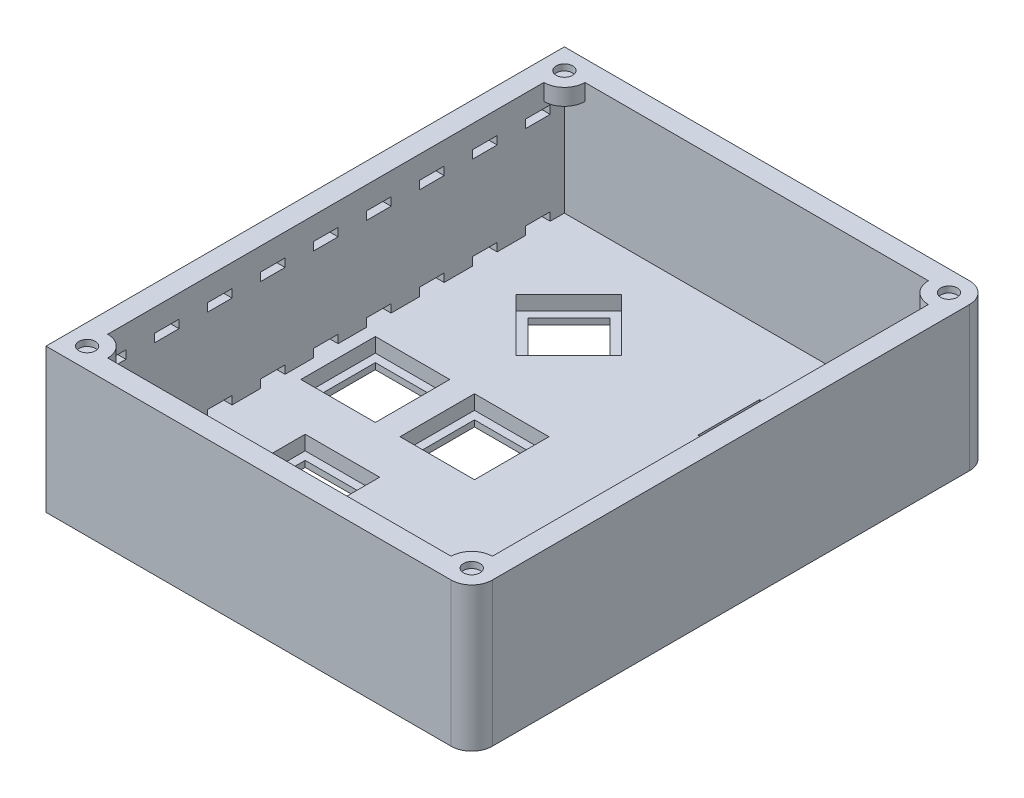
SolidWorks part; units mm, degrees
ref_plane "Front Plane" through (0, 0, 0) normal (0, 0, 1) x (1, 0, 0)
ref_plane "Top Plane" through (0, 0, 0) normal (0, 1, 0) x (1, 0, 0)
ref_plane "Right Plane" through (0, 0, 0) normal (1, 0, 0) x (0, 0, -1)
sketch "Sketch1" plane through (0, 0, 0) normal (0, 1, 0) x (1, 0, 0)
  line L0 (93.4844, 127.7999) -> (93.4844, -14.5462) construction
  line L1 (0, 0) -> (186.9688, 0)
  line L2 (0, 0) -> (0, 116)
  line L3 (0, 116) -> (186.9688, 116)
  line L4 (186.9688, 0) -> (186.9688, 116)
  line L25 (69.3844, 113.4279) -> (69.3844, 11.6856) construction
  line L26 (50.2844, 65.05) -> (64.3844, 65.05)
  line L31 (50.2844, 65.05) -> (50.2844, 50.95)
  line L32 (50.2844, 50.95) -> (64.3844, 50.95)
  line L33 (27.175, 93) -> (0, 93) construction
  line L34 (23, 88.825) -> (23, 116) construction
  line L35 (64.3844, 65.05) -> (64.3844, 50.95)
  line L40 (47.7844, 67.55) -> (47.7844, 48.45)
  line L41 (47.7844, 48.45) -> (66.8844, 48.45)
  line L42 (66.8844, 67.55) -> (66.8844, 48.45)
  line L43 (47.7844, 67.55) -> (66.8844, 67.55)
  line L44 (90.9844, 67.55) -> (90.9844, 48.45)
  line L45 (90.9844, 48.45) -> (71.8844, 48.45)
  line L46 (71.8844, 67.55) -> (71.8844, 48.45)
  line L47 (90.9844, 67.55) -> (71.8844, 67.55)
  line L48 (88.4844, 50.95) -> (74.3844, 50.95)
  line L49 (74.3844, 65.05) -> (74.3844, 50.95)
  line L50 (88.4844, 65.05) -> (74.3844, 65.05)
  line L51 (88.4844, 65.05) -> (88.4844, 50.95)
  line L52 (13.3874, 28.9) -> (54.844, 28.9) construction
  line L53 (62.3344, 35.95) -> (76.4344, 35.95)
  line L54 (62.3344, 35.95) -> (62.3344, 21.85)
  line L63 (62.3344, 21.85) -> (76.4344, 21.85)
  line L64 (-34.0049, 58) -> (152.0549, 58) construction
  line L65 (76.4344, 35.95) -> (76.4344, 21.85)
  line L66 (50.3844, 38.45) -> (88.3844, 38.45)
  line L67 (50.3844, 38.45) -> (50.3844, 19.35)
  line L68 (50.3844, 19.35) -> (88.3844, 19.35)
  line L69 (88.3844, 38.45) -> (88.3844, 19.35)
  line L70 (136.5844, 19.35) -> (98.5844, 19.35)
  line L71 (98.5844, 38.45) -> (98.5844, 19.35)
  line L72 (136.5844, 38.45) -> (98.5844, 38.45)
  line L73 (136.5844, 38.45) -> (136.5844, 19.35)
  line L74 (124.6344, 21.85) -> (110.5344, 21.85)
  line L75 (110.5344, 35.95) -> (110.5344, 21.85)
  line L76 (124.6344, 35.95) -> (110.5344, 35.95)
  line L77 (124.6344, 35.95) -> (124.6344, 21.85)
  line L78 (98.4844, 65.05) -> (98.4844, 50.95)
  line L79 (98.4844, 65.05) -> (112.5844, 65.05)
  line L80 (112.5844, 65.05) -> (112.5844, 50.95)
  line L81 (98.4844, 50.95) -> (112.5844, 50.95)
  line L82 (95.9844, 48.45) -> (115.0844, 48.45)
  line L83 (95.9844, 67.55) -> (95.9844, 48.45)
  line L84 (95.9844, 67.55) -> (115.0844, 67.55)
  line L85 (115.0844, 67.55) -> (115.0844, 48.45)
  line L86 (139.1844, 48.45) -> (120.0844, 48.45)
  line L87 (139.1844, 67.55) -> (139.1844, 48.45)
  line L88 (139.1844, 67.55) -> (120.0844, 67.55)
  line L89 (120.0844, 67.55) -> (120.0844, 48.45)
  line L90 (136.6844, 50.95) -> (122.5844, 50.95)
  line L91 (122.5844, 65.05) -> (122.5844, 50.95)
  line L92 (136.6844, 65.05) -> (122.5844, 65.05)
  line L93 (136.6844, 65.05) -> (136.6844, 50.95)
  line L94 (66.8844, 58.1269) -> (71.8844, 58.1269) construction
  line L95 (90.9844, 58.1269) -> (95.9844, 58.1269) construction
  line L96 (38, 113.0349) -> (38, 79.1538) construction
  line L97 (69.3844, 102.9702) -> (59.4142, 93)
  line L102 (59.4142, 93) -> (69.3844, 83.0298)
  line L103 (69.3844, 83.0298) -> (79.3546, 93)
  line L104 (79.3546, 93) -> (69.3844, 102.9702)
  line L109 (80.7688, 93) -> (69.3844, 104.3844)
  line L110 (69.3844, 104.3844) -> (58, 93)
  line L111 (58, 93) -> (69.3844, 81.6156)
  line L112 (69.3844, 81.6156) -> (80.7688, 93)
  line L113 (117.5844, 81.6156) -> (106.2, 93)
  line L114 (128.9688, 93) -> (117.5844, 81.6156)
  line L115 (117.5844, 104.3844) -> (128.9688, 93)
  line L116 (106.2, 93) -> (117.5844, 104.3844)
  line L117 (117.5844, 83.0298) -> (107.6142, 93)
  line L118 (127.5546, 93) -> (117.5844, 83.0298)
  line L119 (117.5844, 102.9702) -> (127.5546, 93)
  line L120 (107.6142, 93) -> (117.5844, 102.9702)
  line L121 (-5, 0) -> (-5, 116)
  line L122 (0, 121) -> (186.9688, 121)
  line L123 (191.9688, 0) -> (191.9688, 116)
  line L124 (0, -5) -> (186.9688, -5)
  line L125 (191.9688, -5) -> (191.9688, 121) construction
  line L126 (-5, -5) -> (191.9688, -5) construction
  line L127 (-5, 121) -> (191.9688, 121) construction
  line L128 (-5, -5) -> (-5, 121) construction
  line L129 (169.3688, 91.75) -> (158.5688, 91.75)
  line L130 (17.6, 94.25) -> (28.4, 94.25)
  line L131 (17.6, 94.25) -> (17.6, 91.75)
  line L132 (17.6, 91.75) -> (28.4, 91.75)
  line L133 (28.4, 94.25) -> (28.4, 91.75)
  line L134 (158.5688, 94.25) -> (158.5688, 91.75)
  line L135 (169.3688, 94.25) -> (158.5688, 94.25)
  line L136 (169.3688, 94.25) -> (169.3688, 91.75)
  line L137 (23, 88.825) -> (23, 58) construction
  line L138 (27.175, 93) -> (58, 93) construction
  circle A0 centre (23, 93) radius 4.175
  circle A2 centre (23, 93) radius 15
  circle A3 centre (163.9688, 93) radius 15
  circle A4 centre (163.9688, 93) radius 4.175
  arc A6 (0, 121) -> (-5, 116) centre (0, 116) ccw
  arc A7 (-5, 0) -> (0, -5) centre (0, 0) ccw
  arc A8 (186.9688, -5) -> (191.9688, 0) centre (186.9688, 0) ccw
  arc A9 (191.9688, 116) -> (186.9688, 121) centre (186.9688, 116) ccw
  point P31 (69.3844, 35.95)
  point P33 (93.4844, 116)
  point P37 (69.3844, 38.45)
  point P40 (88.3844, 28.9)
  point P41 (76.4344, 28.9)
  point P80 (64.3844, 58)
  point P91 (186.9688, 58)
  point P116 (23, 94.25)
  point P117 (17.6, 93)
  point P122 (38, 79.1538)
  dimension "D3" = 8.35
  dimension "D10" = 5
  dimension "D8" = 30
  dimension "D2" = 2.5
  dimension "D4" = 14.1
  dimension "D5" = 2.5
  dimension "D6" = 5
  dimension "D7" = 19.1
  dimension "D9" = 10.8
  dimension "D11" = 38
  dimension "D12" = 10
  dimension "D14" = 2.5
  dimension "D15" = 20
  dimension "D16" = 126
  dimension "D13" = 1
extrude "Boss-Extrude1" add sketch "Sketch1" against normal blind 5 contours L121 L124 L123 L122 L4 L1 L2 L3 | L1 L4 L3 L2 L113 L116 L115 L114 L84 L85 L82 L83 L40 L43 L42 L41 L47 L44 L45 L46 L66 L69 L68 L67 L72 L73 L70 L71 L89 L88 L87 L86 L112 L111 L110 L109 A2 A3 | A2 A0 | L111 L112 L109 L110 L104 L103 L102 L97 | L116 L113 L114 L115 L117 L120 L119 L118 | A3 A4 | L88 L89 L86 L87 L92 L93 L90 L91 | L85 L84 L83 L82 L81 L78 L79 L80 | L44 L47 L46 L45 L50 L51 L48 L49 | L43 L40 L41 L42 L26 L35 L32 L31 | L69 L66 L67 L68 L53 L65 L63 L54 | L73 L72 L71 L70 L76 L77 L74 L75 region at (93.4844, 0, -56.4932) region at (57.3344, 0, -67.2799) region at (90.7143, 0, -58) region at (69.3844, 0, -38.0247) region at (117.5844, 0, -19.7753) region at (96.2545, 0, -58) region at (129.6344, 0, -48.7201) region at (74.8489, 0, -87.5355) region at (112.1199, 0, -87.5355) region at (-2.6618, 0, -58) region at (8.4243, 0, -93) region at (149.3931, 0, -93)
extrude "Boss-Extrude2" add sketch "Sketch1<3>" along normal blind 30 contours L121 L124 L123 L122 L4 L1 L2 L3 region at (-2.6618, 0, -58)
sketch "Sketch1<3>" plane through (0, 0, 0) normal (0, 1, 0) x (1, 0, 0) same geometry as "Sketch1"
sketch "Sketch3" plane through (0, 0, 0) normal (0, 1, 0) x (1, 0, 0)
  line L23 (48.2844, 67.05) -> (48.2844, 48.95)
  line L24 (48.2844, 48.95) -> (66.3844, 48.95)
  line L25 (66.3844, 48.95) -> (66.3844, 67.05)
  line L26 (66.3844, 67.05) -> (48.2844, 67.05)
  line L27 (48.2844, 67.05) -> (48.2844, 48.95)
  line L28 (48.2844, 48.95) -> (66.3844, 48.95)
  line L29 (66.3844, 48.95) -> (66.3844, 67.05)
  line L30 (66.3844, 67.05) -> (48.2844, 67.05)
  line L35 (69.3844, 105.7986) -> (56.5858, 93)
  line L36 (82.1831, 93) -> (69.3844, 105.7986)
  line L37 (69.3844, 80.2014) -> (82.1831, 93)
  line L38 (56.5858, 93) -> (69.3844, 80.2014)
  line L39 (69.3844, 105.7986) -> (56.5858, 93)
  line L40 (82.1831, 93) -> (69.3844, 105.7986)
  line L41 (69.3844, 80.2014) -> (82.1831, 93)
  line L42 (56.5858, 93) -> (69.3844, 80.2014)
  line L47 (60.3344, 37.95) -> (60.3344, 19.85)
  line L48 (60.3344, 19.85) -> (78.4344, 19.85)
  line L49 (78.4344, 19.85) -> (78.4344, 37.95)
  line L50 (78.4344, 37.95) -> (60.3344, 37.95)
  line L51 (60.3344, 37.95) -> (60.3344, 19.85)
  line L52 (60.3344, 19.85) -> (78.4344, 19.85)
  line L53 (78.4344, 19.85) -> (78.4344, 37.95)
  line L54 (78.4344, 37.95) -> (60.3344, 37.95)
  line L59 (72.3844, 67.05) -> (72.3844, 48.95)
  line L60 (72.3844, 48.95) -> (90.4844, 48.95)
  line L61 (90.4844, 48.95) -> (90.4844, 67.05)
  line L62 (90.4844, 67.05) -> (72.3844, 67.05)
  line L63 (72.3844, 67.05) -> (72.3844, 48.95)
  line L64 (72.3844, 48.95) -> (90.4844, 48.95)
  line L65 (90.4844, 48.95) -> (90.4844, 67.05)
  line L66 (90.4844, 67.05) -> (72.3844, 67.05)
  line L71 (96.4844, 67.05) -> (96.4844, 48.95)
  line L72 (96.4844, 48.95) -> (114.5844, 48.95)
  line L73 (114.5844, 48.95) -> (114.5844, 67.05)
  line L74 (114.5844, 67.05) -> (96.4844, 67.05)
  line L75 (96.4844, 67.05) -> (96.4844, 48.95)
  line L76 (96.4844, 48.95) -> (114.5844, 48.95)
  line L77 (114.5844, 48.95) -> (114.5844, 67.05)
  line L78 (114.5844, 67.05) -> (96.4844, 67.05)
  line L89 (120.5844, 67.05) -> (120.5844, 48.95)
  line L90 (120.5844, 48.95) -> (138.6844, 48.95)
  line L91 (138.6844, 48.95) -> (138.6844, 67.05)
  line L92 (138.6844, 67.05) -> (120.5844, 67.05)
  line L93 (120.5844, 67.05) -> (120.5844, 48.95)
  line L94 (120.5844, 48.95) -> (138.6844, 48.95)
  line L95 (138.6844, 48.95) -> (138.6844, 67.05)
  line L96 (138.6844, 67.05) -> (120.5844, 67.05)
  line L107 (104.7858, 93) -> (117.5844, 80.2014)
  line L108 (117.5844, 80.2014) -> (130.3831, 93)
  line L109 (130.3831, 93) -> (117.5844, 105.7986)
  line L110 (117.5844, 105.7986) -> (104.7858, 93)
  line L111 (104.7858, 93) -> (117.5844, 80.2014)
  line L112 (117.5844, 80.2014) -> (130.3831, 93)
  line L113 (130.3831, 93) -> (117.5844, 105.7986)
  line L114 (117.5844, 105.7986) -> (104.7858, 93)
  line L119 (108.5344, 37.95) -> (108.5344, 19.85)
  line L120 (108.5344, 19.85) -> (126.6344, 19.85)
  line L121 (126.6344, 19.85) -> (126.6344, 37.95)
  line L122 (126.6344, 37.95) -> (108.5344, 37.95)
  line L123 (108.5344, 37.95) -> (108.5344, 19.85)
  line L124 (108.5344, 19.85) -> (126.6344, 19.85)
  line L125 (126.6344, 19.85) -> (126.6344, 37.95)
  line L126 (126.6344, 37.95) -> (108.5344, 37.95)
  dimension "D1" = 2
  dimension "D2" = 2
  dimension "D3" = 2
  dimension "D4" = 2
  dimension "D5" = 2
  dimension "D6" = 2
  dimension "D7" = 2
  dimension "D8" = 2
extrude "Cut-Extrude1" cut sketch "Sketch3" against normal offset from surface (3.5 mm away) 1.5 up to face at (93.4844, -5, -58)
sketch "Sketch4" plane through (0, -5, 0) normal (0, -1, 0) x (1, 0, 0)
  line L0 (0, 5) -> (186.9688, 5) construction
  line L1 (-45.6962, 32.0184) -> (93.4844, 32.0184)
  line L2 (-45.6962, 32.0184) -> (-45.6962, -125.7085)
  line L3 (-45.6962, -125.7085) -> (93.4844, -125.7085)
  line L4 (93.4844, 32.0184) -> (93.4844, -125.7085)
  point P6 (93.4844, 5)
extrude "Cut-Extrude2" cut sketch "Sketch4" against normal through all both and the other way through all
sketch "Sketch5" plane through (0, 0, 0) normal (0, 1, 0) x (1, 0, 0)
  line L0 (169.3688, 94.25) -> (169.3688, 91.75) construction
  line L1 (156.4688, 100.5) -> (171.4688, 100.5)
  line L2 (156.4688, 100.5) -> (156.4688, 85.5)
  line L3 (156.4688, 85.5) -> (171.4688, 85.5)
  line L4 (171.4688, 100.5) -> (171.4688, 85.5)
  arc A0 (159.9854, 91.75) -> (167.9523, 91.75) centre (163.9688, 93) ccw construction
  point P6 (169.3688, 93)
  point P7 (171.4688, 93)
  point P11 (163.9688, 88.825)
  point P12 (163.9688, 85.5)
  dimension "D1" = 15
extrude "Cut-Extrude3" cut sketch "Sketch5" against normal offset from surface 2 and the other way through all up to face at (157.8192, -5, -58)
sketch "Sketch6" plane through (0, -5, 0) normal (0, -1, 0) x (1, 0, 0)
  line L1 (93.4844, 5) -> (88.4844, 5)
  line L2 (93.4844, 5) -> (93.4844, -121)
  line L3 (93.4844, -121) -> (88.4844, -121)
  line L4 (88.4844, 5) -> (88.4844, -121)
  point P5 (93.4844, -121)
  dimension "D1" = 5
extrude "Boss-Extrude3" add sketch "Sketch6" against normal up to surface (35 mm away) up to face at (150.7822, 30, -58)
sketch "Sketch7" plane through (0, 30, 0) normal (0, 1, 0) x (1, 0, 0)
  line L0 (140.2266, 116) -> (140.2266, 27.2743) construction
  line L1 (93.4844, 116) -> (186.9688, 116) construction
  line L2 (88.4844, 121) -> (186.9688, 121) construction
  line L3 (186.9688, 0) -> (186.9688, 116) construction
  line L4 (186.9688, 58) -> (102.9653, 58) construction
  circle A0 centre (93.4844, 116) radius 5
  circle A1 centre (93.4844, 116) radius 2
  circle A2 centre (186.9688, 116) radius 2
  circle A3 centre (186.9688, 116) radius 5
  circle A4 centre (186.9688, 0) radius 2
  circle A5 centre (186.9688, 0) radius 5
  circle A6 centre (93.4844, 0) radius 5
  circle A7 centre (93.4844, 0) radius 2
  line M7 (186.9688, 0) -> (93.4844, 0)
  line M8 (93.4844, 0) -> (93.4844, 116)
  line M9 (93.4844, 116) -> (186.9688, 116)
  line M10 (186.9688, 116) -> (186.9688, 0)
  arc M13 (186.9688, -5) -> (191.9688, 0) centre (186.9688, 0) ccw
  arc M15 (191.9688, 116) -> (186.9688, 121) centre (186.9688, 116) ccw
  dimension "D1" = 4
extrude "Boss-Extrude4" add sketch "Sketch7" against normal blind 4 contours A1 A0 M9 M8 | A1 A0 M8 M9 | A1 M9 M8 | A1 M8 M9 | A3 A2 M10 M9 | A2 M10 M9 | A2 M9 M10 | A3 A2 M9 M10 M15 | A5 A4 M13 M10 M7 | A4 M7 M10 | A4 M10 M7 | A5 A4 M10 M7 | A7 A6 M7 M8 | A7 M7 M8 | A7 M8 M7 | A7 A6 M8 M7 region at (96.9844, 30, -116.1414) region at (95.849, 30, -113.6354) region at (93.2015, 30, -116.2829) region at (94.3332, 30, -115.1512) region at (184.6043, 30, -113.6354) region at (183.5333, 30, -119.4355) region at (93.343, 30, -3.5) region at (95.849, 30, -2.3646) region at (186.12, 30, -115.1512) region at (187.2518, 30, -116.2829) region at (93.2015, 30, 0.2829) region at (94.3332, 30, -0.8488) region at (184.6043, 30, -2.3646) region at (190.4044, 30, -3.4355) region at (186.12, 30, -0.8488) region at (187.2518, 30, 0.2829)
extrude "Cut-Extrude4" cut sketch "Sketch7<3>" against normal blind 1.5 contours A1 M9 M8 | A1 M8 M9 | A2 M9 M10 | A2 M10 M9 | A4 M7 M10 | A4 M10 M7 | A7 M8 M7 | A7 M7 M8 region at (93.2015, 30, -116.2829) region at (94.3332, 30, -115.1512) region at (186.12, 30, -115.1512) region at (187.2518, 30, -116.2829) region at (93.2015, 30, 0.2829) region at (94.3332, 30, -0.8488) region at (186.12, 30, -0.8488) region at (187.2518, 30, 0.2829)
sketch "Sketch7<3>" plane through (0, 30, 0) normal (0, 1, 0) x (1, 0, 0) same geometry as "Sketch7"
sketch "Sketch8" plane through (88.4844, 0, 0) normal (-1, 0, 0) x (0, 0, 1)
  circle A0 centre (0, 0) radius 2
  dimension "D1" = 4
extrude "Cut-Extrude5" cut sketch "Sketch8" against normal blind 1.5
pattern_linear "LPattern1" count 10 spacing 12.8889 along (0, 0, -1) count 2 spacing 25 along (0, 1, 0) of "Cut-Extrude5"
sketch "Sketch9" plane through (88.4844, 0, 0) normal (-1, 0, 0) x (0, 0, 1)
  line L0 (0, 0) -> (-12.8889, 0) construction
  line L1 (0, 0) -> (-116, 0) construction
  line L2 (-6.4444, 33.7394) -> (-6.4444, -16.9843) construction
  line L7 (-9.4444, 0) -> (-3.4444, 0)
  line L8 (-9.4444, 0) -> (-9.4444, 2)
  line L9 (-9.4444, 2) -> (-3.4444, 2)
  line L10 (-3.4444, 0) -> (-3.4444, 2)
  line L11 (-9.4444, 0) -> (-3.4444, 2) construction
  line L12 (-9.4444, 2) -> (-3.4444, 0) construction
  point P4 (-6.4444, 0)
  point P7 (-6.4444, 0)
  point P8 (-6.4444, 1)
  dimension "D1" = 12.8889
  dimension "D2" = 6
  dimension "D3" = 2
extrude "Cut-Extrude6" cut sketch "Sketch9" against normal up to surface (5 mm away) up to face at (93.4844, 20.5, -58)
pattern_linear "LPattern2" count 9 spacing 12.8889 along (0, 0, -1) count 2 spacing 22.5 along (0, 1, 0) of "Cut-Extrude6"
equation "\"Hole Spacing\"= \"D1@Sketch9\""
equation "\"D3@LPattern2\"=\"Hole Spacing\""
